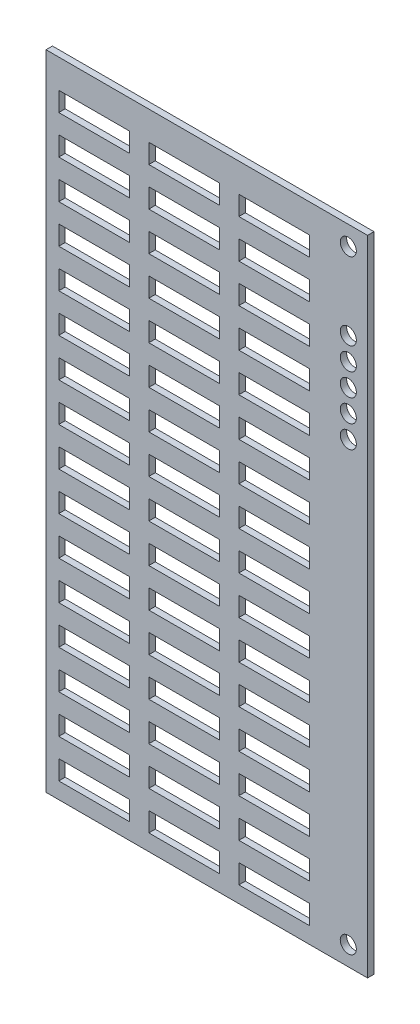
SolidWorks part; units mm, degrees
ref_plane "Plan de face" through (0, 0, 0) normal (0, 0, 1) x (1, 0, 0)
ref_plane "Plan de dessus" through (0, 0, 0) normal (0, 1, 0) x (1, 0, 0)
ref_plane "Plan de droite" through (0, 0, 0) normal (1, 0, 0) x (0, 0, -1)
sketch "Esquisse1" plane through (0, 0, 0) normal (0, 0, 1) x (1, 0, 0)
  line L0 (0, 0) -> (0, -50000) construction
  line L1 (-250, 500) -> (250, 500)
  line L2 (-250, 500) -> (-250, -500)
  line L3 (-250, -500) -> (250, -500)
  line L4 (250, 500) -> (250, -500)
  line L5 (-250, 500) -> (250, -500) construction
  line L6 (-250, -500) -> (250, 500) construction
  line L7 (0, 0) -> (50000, 0) construction
  line L8 (220, 470) -> (220, 500) construction
  line L9 (220, 470) -> (250, 470) construction
  line L10 (220, 350) -> (220, 315) construction
  line L11 (220, 315) -> (220, 280) construction
  line L12 (220, 280) -> (220, 245) construction
  line L13 (220, 245) -> (220, 210) construction
  line L14 (220, 210) -> (220, -500) construction
  line L15 (220, 350) -> (220, 500) construction
  circle A0 centre (220, 470) radius 12.5
  circle A2 centre (220, -470) radius 12.5
  circle A3 centre (220, 350) radius 12.5
  circle A4 centre (220, 315) radius 12.5
  circle A5 centre (220, 245) radius 12.5
  circle A6 centre (220, 280) radius 12.5
  circle A7 centre (220, 210) radius 12.5
  point P0 (0, 0)
  dimension "D3" = 25
  dimension "D5" = 25
  dimension "D1" = 1000
  dimension "D2" = 500
  dimension "D4" = 30
  dimension "D6" = 35
  dimension "D7" = 30
  dimension "D10" = 150
extrude "Boss.-Extru.1" add sketch "Esquisse1" along normal blind 10
sketch "Esquisse3" plane through (0, 0, 10) normal (0, 0, 1) x (1, 0, 0)
  line L0 (-250, 440.3401) -> (250, 440.3401) construction
  line L1 (-230.1295, 455.3401) -> (-120.1295, 455.3401)
  line L2 (-230.1295, 455.3401) -> (-230.1295, 425.3401)
  line L3 (-230.1295, 425.3401) -> (-120.1295, 425.3401)
  line L4 (-120.1295, 455.3401) -> (-120.1295, 425.3401)
  line L5 (-230.1295, 455.3401) -> (-120.1295, 425.3401) construction
  line L6 (-230.1295, 425.3401) -> (-120.1295, 455.3401) construction
  line L7 (-250, 500) -> (-250, -500) construction
  line L8 (250, -500) -> (250, 500) construction
  line L9 (-90.1295, 455.3401) -> (19.8705, 455.3401)
  line L10 (-90.1295, 455.3401) -> (-90.1295, 425.3401)
  line L11 (-90.1295, 425.3401) -> (19.8705, 425.3401)
  line L12 (19.8705, 455.3401) -> (19.8705, 425.3401)
  line L13 (49.8705, 455.3401) -> (159.8705, 455.3401)
  line L14 (49.8705, 455.3401) -> (49.8705, 425.3401)
  line L15 (49.8705, 425.3401) -> (159.8705, 425.3401)
  line L16 (159.8705, 455.3401) -> (159.8705, 425.3401)
  line L17 (-90.1295, 395.3401) -> (19.8705, 395.3401)
  line L18 (-90.1295, 395.3401) -> (-90.1295, 365.3401)
  line L19 (-90.1295, 365.3401) -> (19.8705, 365.3401)
  line L20 (19.8705, 395.3401) -> (19.8705, 365.3401)
  line L21 (49.8705, 395.3401) -> (159.8705, 395.3401)
  line L22 (49.8705, 395.3401) -> (49.8705, 365.3401)
  line L23 (49.8705, 365.3401) -> (159.8705, 365.3401)
  line L24 (159.8705, 395.3401) -> (159.8705, 365.3401)
  line L25 (-90.1295, 335.3401) -> (19.8705, 335.3401)
  line L26 (-90.1295, 335.3401) -> (-90.1295, 305.3401)
  line L27 (-90.1295, 305.3401) -> (19.8705, 305.3401)
  line L28 (19.8705, 335.3401) -> (19.8705, 305.3401)
  line L29 (49.8705, 335.3401) -> (159.8705, 335.3401)
  line L30 (49.8705, 335.3401) -> (49.8705, 305.3401)
  line L31 (49.8705, 305.3401) -> (159.8705, 305.3401)
  line L32 (159.8705, 335.3401) -> (159.8705, 305.3401)
  line L33 (-90.1295, 275.3401) -> (19.8705, 275.3401)
  line L34 (-90.1295, 275.3401) -> (-90.1295, 245.3401)
  line L35 (-90.1295, 245.3401) -> (19.8705, 245.3401)
  line L36 (19.8705, 275.3401) -> (19.8705, 245.3401)
  line L37 (49.8705, 275.3401) -> (159.8705, 275.3401)
  line L38 (49.8705, 275.3401) -> (49.8705, 245.3401)
  line L39 (49.8705, 245.3401) -> (159.8705, 245.3401)
  line L40 (159.8705, 275.3401) -> (159.8705, 245.3401)
  line L41 (-90.1295, 215.3401) -> (19.8705, 215.3401)
  line L42 (-90.1295, 215.3401) -> (-90.1295, 185.3401)
  line L43 (-90.1295, 185.3401) -> (19.8705, 185.3401)
  line L44 (19.8705, 215.3401) -> (19.8705, 185.3401)
  line L45 (49.8705, 215.3401) -> (159.8705, 215.3401)
  line L46 (49.8705, 215.3401) -> (49.8705, 185.3401)
  line L47 (49.8705, 185.3401) -> (159.8705, 185.3401)
  line L48 (159.8705, 215.3401) -> (159.8705, 185.3401)
  line L49 (-90.1295, 155.3401) -> (19.8705, 155.3401)
  line L50 (-90.1295, 155.3401) -> (-90.1295, 125.3401)
  line L51 (-90.1295, 125.3401) -> (19.8705, 125.3401)
  line L52 (19.8705, 155.3401) -> (19.8705, 125.3401)
  line L53 (49.8705, 155.3401) -> (159.8705, 155.3401)
  line L54 (49.8705, 155.3401) -> (49.8705, 125.3401)
  line L55 (49.8705, 125.3401) -> (159.8705, 125.3401)
  line L56 (159.8705, 155.3401) -> (159.8705, 125.3401)
  line L57 (-90.1295, 95.3401) -> (19.8705, 95.3401)
  line L58 (-90.1295, 95.3401) -> (-90.1295, 65.3401)
  line L59 (-90.1295, 65.3401) -> (19.8705, 65.3401)
  line L60 (19.8705, 95.3401) -> (19.8705, 65.3401)
  line L61 (49.8705, 95.3401) -> (159.8705, 95.3401)
  line L62 (49.8705, 95.3401) -> (49.8705, 65.3401)
  line L63 (49.8705, 65.3401) -> (159.8705, 65.3401)
  line L64 (159.8705, 95.3401) -> (159.8705, 65.3401)
  line L65 (-90.1295, 35.3401) -> (19.8705, 35.3401)
  line L66 (-90.1295, 35.3401) -> (-90.1295, 5.3401)
  line L67 (-90.1295, 5.3401) -> (19.8705, 5.3401)
  line L68 (19.8705, 35.3401) -> (19.8705, 5.3401)
  line L69 (49.8705, 35.3401) -> (159.8705, 35.3401)
  line L70 (49.8705, 35.3401) -> (49.8705, 5.3401)
  line L71 (49.8705, 5.3401) -> (159.8705, 5.3401)
  line L72 (159.8705, 35.3401) -> (159.8705, 5.3401)
  line L73 (-90.1295, -24.6599) -> (19.8705, -24.6599)
  line L74 (-90.1295, -24.6599) -> (-90.1295, -54.6599)
  line L75 (-90.1295, -54.6599) -> (19.8705, -54.6599)
  line L76 (19.8705, -24.6599) -> (19.8705, -54.6599)
  line L77 (49.8705, -24.6599) -> (159.8705, -24.6599)
  line L78 (49.8705, -24.6599) -> (49.8705, -54.6599)
  line L79 (49.8705, -54.6599) -> (159.8705, -54.6599)
  line L80 (159.8705, -24.6599) -> (159.8705, -54.6599)
  line L81 (-90.1295, -84.6599) -> (19.8705, -84.6599)
  line L82 (-90.1295, -84.6599) -> (-90.1295, -114.6599)
  line L83 (-90.1295, -114.6599) -> (19.8705, -114.6599)
  line L84 (19.8705, -84.6599) -> (19.8705, -114.6599)
  line L85 (49.8705, -84.6599) -> (159.8705, -84.6599)
  line L86 (49.8705, -84.6599) -> (49.8705, -114.6599)
  line L87 (49.8705, -114.6599) -> (159.8705, -114.6599)
  line L88 (159.8705, -84.6599) -> (159.8705, -114.6599)
  line L89 (-90.1295, -144.6599) -> (19.8705, -144.6599)
  line L90 (-90.1295, -144.6599) -> (-90.1295, -174.6599)
  line L91 (-90.1295, -174.6599) -> (19.8705, -174.6599)
  line L92 (19.8705, -144.6599) -> (19.8705, -174.6599)
  line L93 (49.8705, -144.6599) -> (159.8705, -144.6599)
  line L94 (49.8705, -144.6599) -> (49.8705, -174.6599)
  line L95 (49.8705, -174.6599) -> (159.8705, -174.6599)
  line L96 (159.8705, -144.6599) -> (159.8705, -174.6599)
  line L97 (-90.1295, -204.6599) -> (19.8705, -204.6599)
  line L98 (-90.1295, -204.6599) -> (-90.1295, -234.6599)
  line L99 (-90.1295, -234.6599) -> (19.8705, -234.6599)
  line L100 (19.8705, -204.6599) -> (19.8705, -234.6599)
  line L101 (49.8705, -204.6599) -> (159.8705, -204.6599)
  line L102 (49.8705, -204.6599) -> (49.8705, -234.6599)
  line L103 (49.8705, -234.6599) -> (159.8705, -234.6599)
  line L104 (159.8705, -204.6599) -> (159.8705, -234.6599)
  line L105 (-90.1295, -264.6599) -> (19.8705, -264.6599)
  line L106 (-90.1295, -264.6599) -> (-90.1295, -294.6599)
  line L107 (-90.1295, -294.6599) -> (19.8705, -294.6599)
  line L108 (19.8705, -264.6599) -> (19.8705, -294.6599)
  line L109 (49.8705, -264.6599) -> (159.8705, -264.6599)
  line L110 (49.8705, -264.6599) -> (49.8705, -294.6599)
  line L111 (49.8705, -294.6599) -> (159.8705, -294.6599)
  line L112 (159.8705, -264.6599) -> (159.8705, -294.6599)
  line L113 (-90.1295, -324.6599) -> (19.8705, -324.6599)
  line L114 (-90.1295, -324.6599) -> (-90.1295, -354.6599)
  line L115 (-90.1295, -354.6599) -> (19.8705, -354.6599)
  line L116 (19.8705, -324.6599) -> (19.8705, -354.6599)
  line L117 (49.8705, -324.6599) -> (159.8705, -324.6599)
  line L118 (49.8705, -324.6599) -> (49.8705, -354.6599)
  line L119 (49.8705, -354.6599) -> (159.8705, -354.6599)
  line L120 (159.8705, -324.6599) -> (159.8705, -354.6599)
  line L121 (-90.1295, -384.6599) -> (19.8705, -384.6599)
  line L122 (-90.1295, -384.6599) -> (-90.1295, -414.6599)
  line L123 (-90.1295, -414.6599) -> (19.8705, -414.6599)
  line L124 (19.8705, -384.6599) -> (19.8705, -414.6599)
  line L125 (49.8705, -384.6599) -> (159.8705, -384.6599)
  line L126 (49.8705, -384.6599) -> (49.8705, -414.6599)
  line L127 (49.8705, -414.6599) -> (159.8705, -414.6599)
  line L128 (159.8705, -384.6599) -> (159.8705, -414.6599)
  line L129 (-90.1295, -444.6599) -> (19.8705, -444.6599)
  line L130 (-90.1295, -444.6599) -> (-90.1295, -474.6599)
  line L131 (-90.1295, -474.6599) -> (19.8705, -474.6599)
  line L132 (19.8705, -444.6599) -> (19.8705, -474.6599)
  line L133 (49.8705, -444.6599) -> (159.8705, -444.6599)
  line L134 (49.8705, -444.6599) -> (49.8705, -474.6599)
  line L135 (49.8705, -474.6599) -> (159.8705, -474.6599)
  line L136 (159.8705, -444.6599) -> (159.8705, -474.6599)
  line L137 (-230.1295, 395.3401) -> (-120.1295, 395.3401)
  line L138 (-230.1295, 395.3401) -> (-230.1295, 365.3401)
  line L139 (-230.1295, 365.3401) -> (-120.1295, 365.3401)
  line L140 (-120.1295, 395.3401) -> (-120.1295, 365.3401)
  line L141 (-230.1295, 335.3401) -> (-120.1295, 335.3401)
  line L142 (-230.1295, 335.3401) -> (-230.1295, 305.3401)
  line L143 (-230.1295, 305.3401) -> (-120.1295, 305.3401)
  line L144 (-120.1295, 335.3401) -> (-120.1295, 305.3401)
  line L145 (-230.1295, 275.3401) -> (-120.1295, 275.3401)
  line L146 (-230.1295, 275.3401) -> (-230.1295, 245.3401)
  line L147 (-230.1295, 245.3401) -> (-120.1295, 245.3401)
  line L148 (-120.1295, 275.3401) -> (-120.1295, 245.3401)
  line L149 (-230.1295, 215.3401) -> (-120.1295, 215.3401)
  line L150 (-230.1295, 215.3401) -> (-230.1295, 185.3401)
  line L151 (-230.1295, 185.3401) -> (-120.1295, 185.3401)
  line L152 (-120.1295, 215.3401) -> (-120.1295, 185.3401)
  line L153 (-230.1295, 155.3401) -> (-120.1295, 155.3401)
  line L154 (-230.1295, 155.3401) -> (-230.1295, 125.3401)
  line L155 (-230.1295, 125.3401) -> (-120.1295, 125.3401)
  line L156 (-120.1295, 155.3401) -> (-120.1295, 125.3401)
  line L157 (-230.1295, 95.3401) -> (-120.1295, 95.3401)
  line L158 (-230.1295, 95.3401) -> (-230.1295, 65.3401)
  line L159 (-230.1295, 65.3401) -> (-120.1295, 65.3401)
  line L160 (-120.1295, 95.3401) -> (-120.1295, 65.3401)
  line L161 (-230.1295, 35.3401) -> (-120.1295, 35.3401)
  line L162 (-230.1295, 35.3401) -> (-230.1295, 5.3401)
  line L163 (-230.1295, 5.3401) -> (-120.1295, 5.3401)
  line L164 (-120.1295, 35.3401) -> (-120.1295, 5.3401)
  line L165 (-230.1295, -24.6599) -> (-120.1295, -24.6599)
  line L166 (-230.1295, -24.6599) -> (-230.1295, -54.6599)
  line L167 (-230.1295, -54.6599) -> (-120.1295, -54.6599)
  line L168 (-120.1295, -24.6599) -> (-120.1295, -54.6599)
  line L169 (-230.1295, -84.6599) -> (-120.1295, -84.6599)
  line L170 (-230.1295, -84.6599) -> (-230.1295, -114.6599)
  line L171 (-230.1295, -114.6599) -> (-120.1295, -114.6599)
  line L172 (-120.1295, -84.6599) -> (-120.1295, -114.6599)
  line L173 (-230.1295, -144.6599) -> (-120.1295, -144.6599)
  line L174 (-230.1295, -144.6599) -> (-230.1295, -174.6599)
  line L175 (-230.1295, -174.6599) -> (-120.1295, -174.6599)
  line L176 (-120.1295, -144.6599) -> (-120.1295, -174.6599)
  line L177 (-230.1295, -204.6599) -> (-120.1295, -204.6599)
  line L178 (-230.1295, -204.6599) -> (-230.1295, -234.6599)
  line L179 (-230.1295, -234.6599) -> (-120.1295, -234.6599)
  line L180 (-120.1295, -204.6599) -> (-120.1295, -234.6599)
  line L181 (-230.1295, -264.6599) -> (-120.1295, -264.6599)
  line L182 (-230.1295, -264.6599) -> (-230.1295, -294.6599)
  line L183 (-230.1295, -294.6599) -> (-120.1295, -294.6599)
  line L184 (-120.1295, -264.6599) -> (-120.1295, -294.6599)
  line L185 (-230.1295, -324.6599) -> (-120.1295, -324.6599)
  line L186 (-230.1295, -324.6599) -> (-230.1295, -354.6599)
  line L187 (-230.1295, -354.6599) -> (-120.1295, -354.6599)
  line L188 (-120.1295, -324.6599) -> (-120.1295, -354.6599)
  line L189 (-230.1295, -384.6599) -> (-120.1295, -384.6599)
  line L190 (-230.1295, -384.6599) -> (-230.1295, -414.6599)
  line L191 (-230.1295, -414.6599) -> (-120.1295, -414.6599)
  line L192 (-120.1295, -384.6599) -> (-120.1295, -414.6599)
  line L193 (-230.1295, -444.6599) -> (-120.1295, -444.6599)
  line L194 (-230.1295, -444.6599) -> (-230.1295, -474.6599)
  line L195 (-230.1295, -474.6599) -> (-120.1295, -474.6599)
  line L196 (-120.1295, -444.6599) -> (-120.1295, -474.6599)
  line L197 (-250, 0) -> (49750, 0) construction
  line L198 (0, 0) -> (0, -50000) construction
  point P0 (-175.1295, 440.3401)
  point P13 (-250, 0)
  dimension "D1" = 110
  dimension "D2" = 30
  dimension "D3" = 3
  dimension "D4" = 16
extrude "Enlèv. mat.-Extru.2" cut sketch "Esquisse3" against normal up to surface (10 mm away) up to face at (0, 0, 0)
